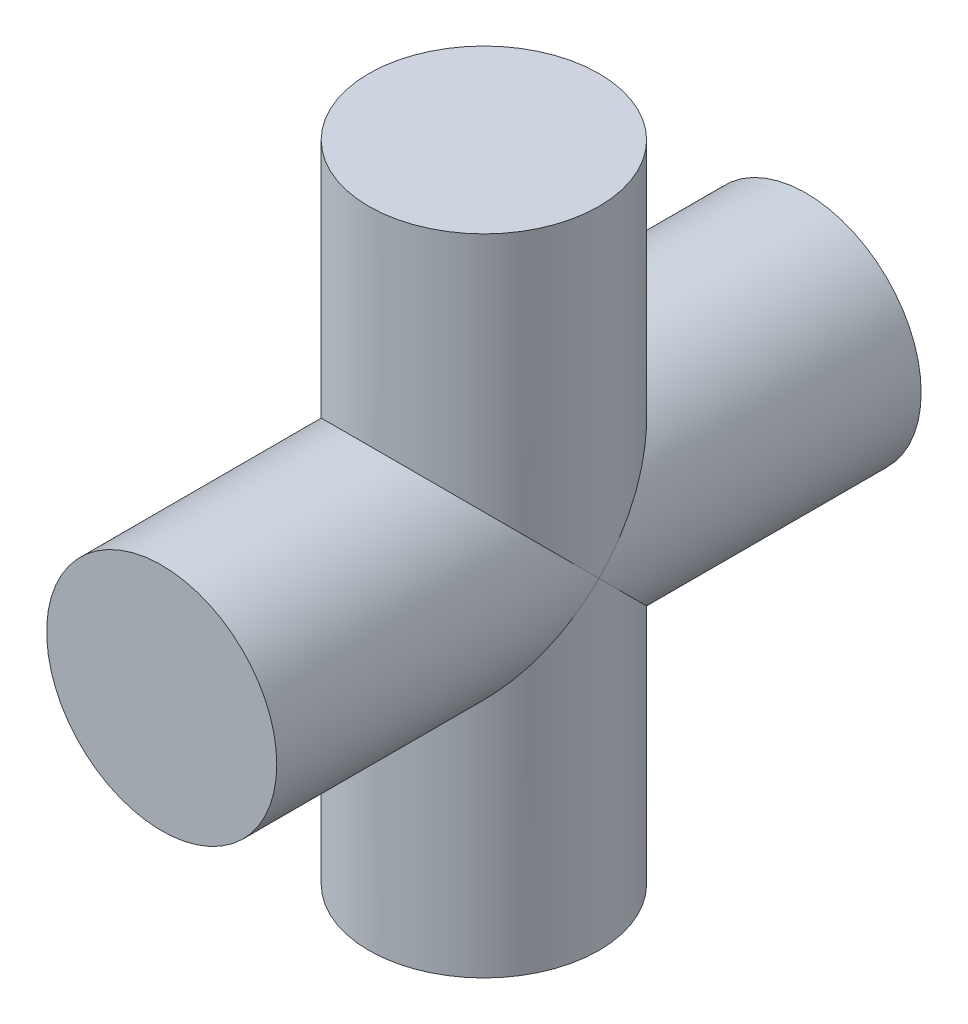
SolidWorks part; units mm, degrees
material "1.0503 (C45)"
ref_plane "Płaszczyzna przednia" through (0, 0, 0) normal (0, 0, 1) x (1, 0, 0)
ref_plane "Płaszczyzna górna" through (0, 0, 0) normal (0, 1, 0) x (1, 0, 0)
ref_plane "Płaszczyzna prawa" through (0, 0, 0) normal (1, 0, 0) x (0, 0, -1)
sketch "Szkic1" plane through (0, 0, 0) normal (0, 0, 1) x (1, 0, 0)
  circle A0 centre (0, 0) radius 7.5
  dimension "D1" = 15
extrude "Dodanie-wyciągnięcie1" add sketch "Szkic1" against normal blind 21 and the other way blind 21
sketch "Szkic2" plane through (0, 0, 0) normal (0, 1, 0) x (1, 0, 0)
  circle A0 centre (0, 0) radius 7.5
  dimension "D1" = 15
extrude "Dodanie-wyciągnięcie2" add sketch "Szkic2" against normal blind 21 and the other way blind 21
